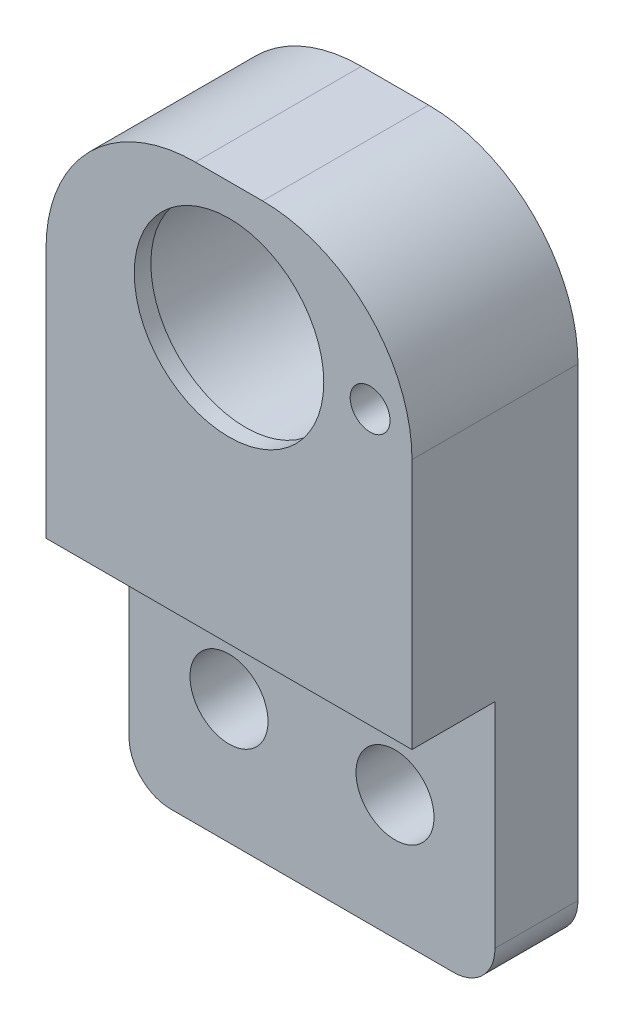
SolidWorks part; units mm, degrees
note: The reader was unsure of these and kept them because the rebuilt part matched: shared geometry of "Sketch1<3>", "Sketch1<4>".
ref_plane "Front Plane" through (0, 0, 0) normal (0, 0, 1) x (1, 0, 0)
ref_plane "Top Plane" through (0, 0, 0) normal (0, 1, 0) x (1, 0, 0)
ref_plane "Right Plane" through (0, 0, 0) normal (1, 0, 0) x (0, 0, -1)
sketch "Sketch1" plane through (0, 0, 0) normal (0, 0, 1) x (1, 0, 0)
  line L68 (36.0314, 66.7147) -> (57.6814, 66.7147)
  line L69 (32.8564, 69.8897) -> (32.8564, 105.4497)
  line L70 (32.8564, 86.2397) -> (60.8564, 86.2397)
  line L71 (60.8564, 69.8897) -> (60.8564, 105.4497)
  line L72 (49.4264, 116.8797) -> (44.2864, 116.8797)
  arc A70 (60.8564, 105.4497) -> (49.4264, 116.8797) centre (49.4264, 105.4497) ccw
  arc A71 (44.2864, 116.8797) -> (32.8564, 105.4497) centre (44.2864, 105.4497) ccw
  circle A72 centre (46.8564, 107.1967) radius 7.9248
  circle A73 centre (46.8564, 107.1967) radius 7.25
  arc A74 (32.8564, 69.8897) -> (36.0314, 66.7147) centre (36.0314, 69.8897) ccw
  arc A75 (57.6814, 66.7147) -> (60.8564, 69.8897) centre (57.6814, 69.8897) ccw
  circle A76 centre (40.5064, 76.2397) radius 2.9845
  circle A77 centre (53.2064, 76.2397) radius 2.9845
  circle A78 centre (57.6514, 107.1967) radius 1.524
extrude "Boss-Extrude1" add sketch "Sketch1" along normal blind 12.7 contours L72 A71 L69 L70 L71 A70 A78 A72 | L68 A75 L71 L70 L69 A74 A77 A76 | A72 A73
extrude "Cut-Extrude1" cut sketch "Sketch1<3>" along normal blind 11.43 contours A72 A73
sketch "Sketch1<3>" plane through (0, 0, 0) normal (0, 0, 1) x (1, 0, 0) same geometry as "Sketch1"
extrude "Cut-Extrude2" cut sketch "Sketch1<4>" against normal blind 6.35 from offset 12.7 contours L68 A75 L71 L70 L69 A74 A77 A76
sketch "Sketch1<4>" plane through (0, 0, 0) normal (0, 0, 1) x (1, 0, 0) same geometry as "Sketch1"
